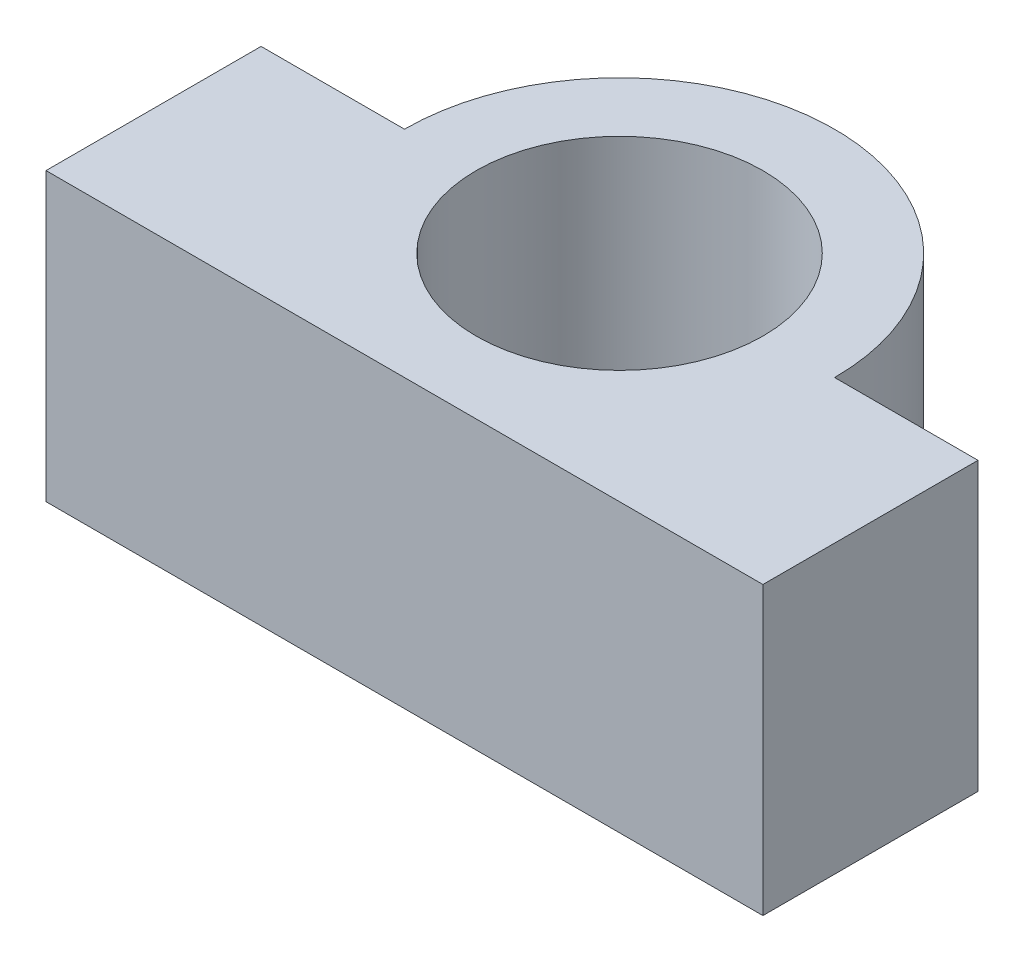
SolidWorks part; units mm, degrees
ref_plane "Front Plane" through (0, 0, 0) normal (0, 0, 1) x (1, 0, 0)
ref_plane "Top Plane" through (0, 0, 0) normal (0, 1, 0) x (1, 0, 0)
ref_plane "Right Plane" through (0, 0, 0) normal (1, 0, 0) x (0, 0, -1)
sketch "Sketch2" plane through (0, 0, 0) normal (0, 1, 0) x (1, 0, 0)
  line L0 (-50, 0) -> (0, 0)
  line L1 (0, 0) -> (0, 15)
  line L2 (0, 15) -> (-10, 15)
  line L3 (-40, 15) -> (-50, 15)
  line L4 (-50, 15) -> (-50, 0)
  arc A0 (-10, 15) -> (-40, 15) centre (-25, 15) ccw
  point P6 (-37.2741, 20.8151)
  point P9 (-38.1226, 19.6991)
  point P10 (-5.584, 15)
  point P11 (0, 0)
  dimension "D1" = 15
  dimension "D2" = 50
  dimension "D3" = 10
  dimension "D4" = 15
extrude "Boss-Extrude1" add sketch "Sketch2" along normal blind 20
sketch "Sketch3" plane through (0, 0, 0) normal (0, -1, 0) x (-1, 0, 0)
  circle A0 centre (25, 15) radius 10
  dimension "D1" = 20
extrude "Cut-Extrude1" cut sketch "Sketch3" against normal through all
